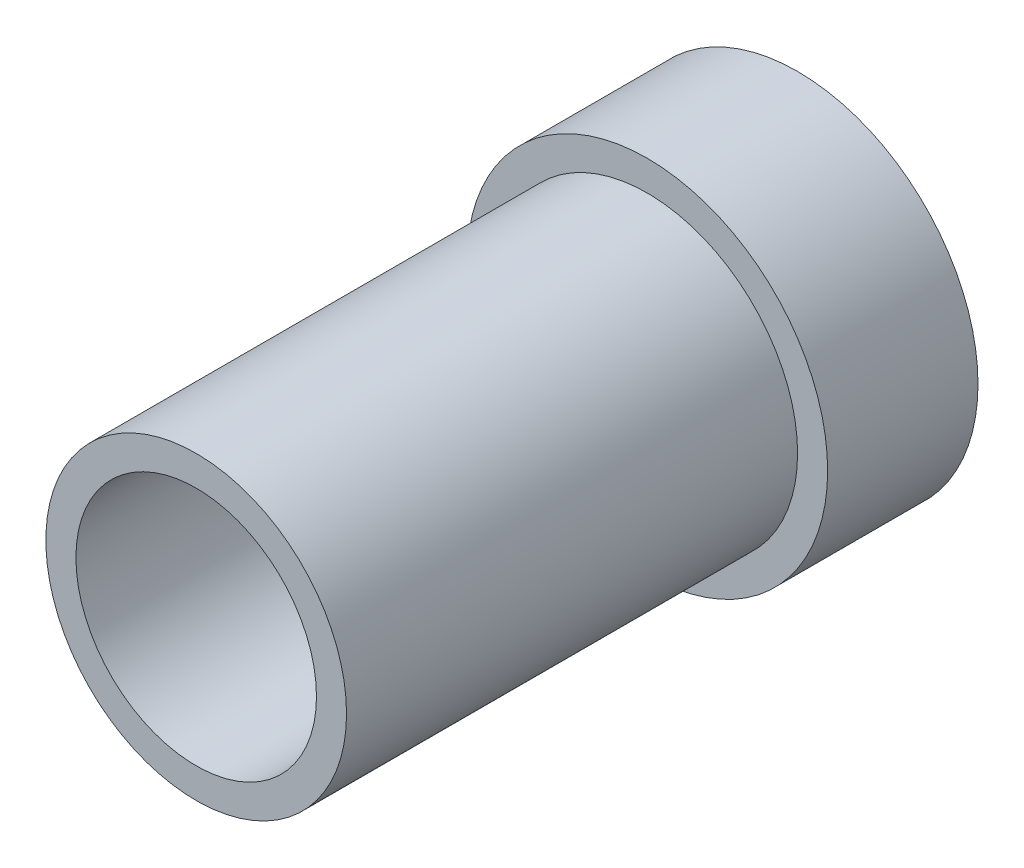
SolidWorks part; units mm, degrees
ref_plane "Alzado" through (0, 0, 0) normal (0, 0, 1) x (1, 0, 0)
ref_plane "Planta" through (0, 0, 0) normal (0, 1, 0) x (1, 0, 0)
ref_plane "Vista lateral" through (0, 0, 0) normal (1, 0, 0) x (0, 0, -1)
sketch "Croquis1" plane through (0, 0, 0) normal (0, 0, 1) x (1, 0, 0)
  circle A0 centre (0, 0) radius 0.8
  circle A1 centre (0, 0) radius 1
  circle A2 centre (0, 0) radius 1.2
  dimension "D1" = 1.6
  dimension "D2" = 2
  dimension "D3" = 2.4
extrude "Saliente-Extruir1" add sketch "Croquis1" along normal blind 3 contours A1 A0 region at (-0.9717, 0, 0)
extrude "Saliente-Extruir2" add sketch "Croquis1<3>" against normal blind 1 contours A2
sketch "Croquis1<3>" plane through (0, 0, 0) normal (0, 0, 1) x (1, 0, 0) same geometry as "Croquis1"
